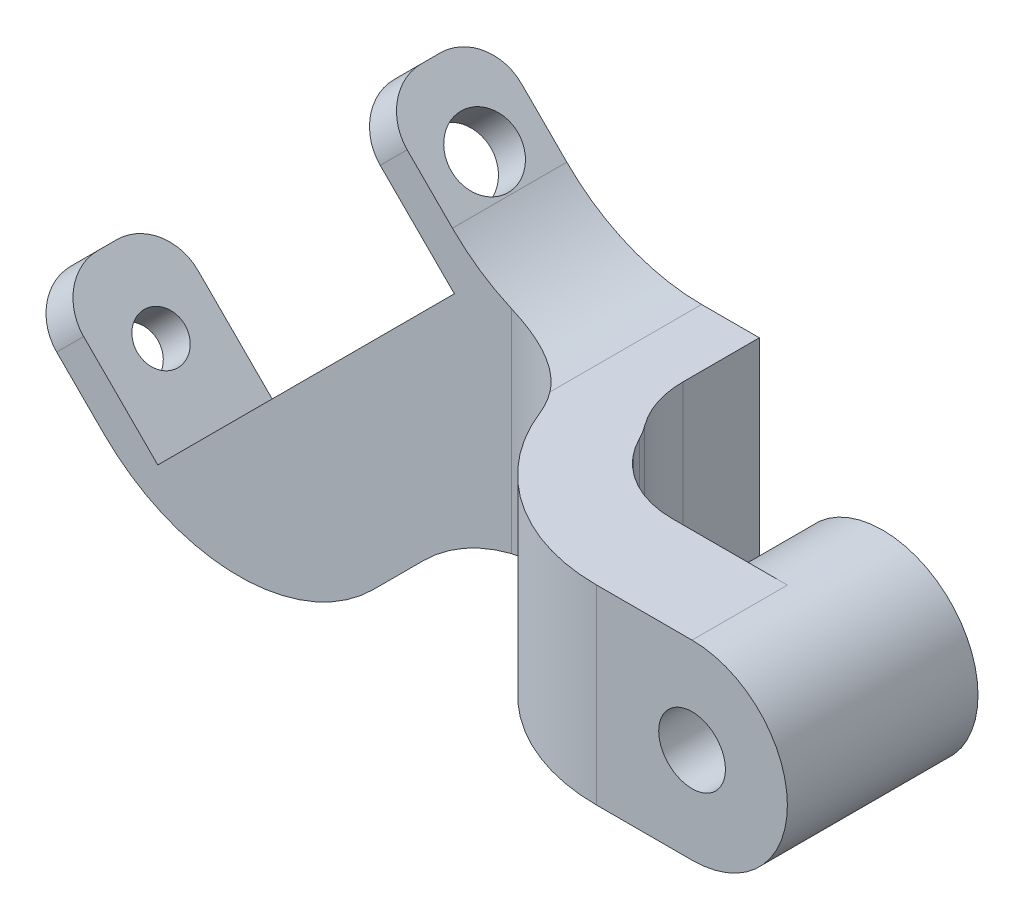
SolidWorks part; units mm, degrees
material "PET"
ref_plane "Piano frontale" through (0, 0, 0) normal (0, 0, 1) x (1, 0, 0)
ref_plane "Piano superiore" through (0, 0, 0) normal (0, 1, 0) x (1, 0, 0)
ref_plane "Piano destro" through (0, 0, 0) normal (1, 0, 0) x (0, 0, -1)
sketch "Schizzo1" plane through (0, 0, 0) normal (0, 0, 1) x (1, 0, 0)
  line L0 (0, 0) -> (-20, 0)
  line L1 (-20, 0) -> (-10, 10)
  line L2 (-10, 10) -> (10, 10)
  line L4 (10, 0) -> (0, 0)
  arc A0 (10, 0) -> (10, 10) centre (10, 5) ccw
  dimension "D6" = 10
  dimension "D1" = 20
  dimension "D2" = 10
  dimension "D3" = 10
  dimension "D4" = 0
  dimension "D5" = 20
extrude "Estrusione-Estrusione1" add sketch "Schizzo1" along normal blind 6 contours L2 A0 L4 L0 L1
sketch "Schizzo3" plane through (0, 0, 6) normal (0, 0, 1) x (1, 0, 0)
  arc A0 (10, 0) -> (10, 10) centre (10, 5) ccw construction
  arc A1 (10, 0) -> (10, 10) centre (10, 5) ccw construction
  circle A2 centre (10, 5) radius 5
  circle A3 centre (10, 5) radius 2.65
  dimension "D1" = 5.3
extrude "Estrusione-Estrusione3" add sketch "Schizzo3" against normal blind 11
sketch "Schizzo4" plane through (0, 0, 6) normal (0, 0, 1) x (1, 0, 0)
  line L0 (-10, 10) -> (-16.0795, 16.0795)
  line L1 (-20, 0) -> (-10, 10) construction
ref_plane "Piano1" through (0, 0, 0) normal (0.7071, 0.7071, 0) x (-0.7071, 0.7071, 0)
sketch "Schizzo5" plane through (0, 0, 0) normal (0.7071, 0.7071, 0) x (-0.7071, 0.7071, 0)
  line L0 (14.1421, 3) -> (18.1421, 3)
  line L1 (14.1421, 6) -> (14.1421, 0) construction
  circle A0 centre (18.1421, 3) radius 0.925
  dimension "D2" = 1.85
  dimension "D1" = 4
extrude "Estrusione-Estrusione4" add sketch "Schizzo5" against normal blind 20 separate body contours A0 region at (-12.8284, 12.8284, 2.1012)
sketch "Schizzo12" plane through (0, 0, 0) normal (0.7071, 0.7071, 0) x (-0.7071, 0.7071, 0)
  line L0 (14.1421, 0) -> (0, 0) construction
  line L1 (14.1421, 6) -> (22.1421, 6)
  line L2 (14.1421, 6) -> (14.1421, 0)
  line L3 (14.1421, 0) -> (22.1421, 0)
  line L4 (22.1421, 6) -> (22.1421, 0)
  dimension "D1" = 8
extrude "Estrusione-Estrusione6" add sketch "Schizzo12" along normal blind 2
sketch "Schizzo13" plane through (-10, 10, 0) normal (0.7071, -0.7071, 0) x (0, 0, -1)
  line L4 (-6, 0) -> (0, 0)
  line L5 (0, 0) -> (0, 2)
  line L6 (0, 2) -> (-6, 2)
  line L7 (-6, 2) -> (-6, 0)
  line L8 (-6, 0) -> (0, 0)
  line L9 (0, 0) -> (0, 2)
  line L10 (0, 2) -> (-6, 2)
  line L11 (-6, 2) -> (-6, 0)
  dimension "D1" = 0
extrude "Estrusione-Estrusione7" add sketch "Schizzo13" along normal blind 3
fillet "Raccordo2" radius 2.5 2 edges at (-14.9497, 16.364, 0) (-14.9497, 16.364, 6)
sketch "Schizzo14" plane through (1.4142, 1.4142, 0) normal (0.7071, 0.7071, 0) x (0, 0, -1)
  circle A0 centre (-3, 18.1421) radius 1.75
  circle A1 centre (-3, 18.1421) radius 0.925
  circle A2 centre (-3, 18.1421) radius 0.925
  dimension "D2" = 3.5
  dimension "D1" = 0
extrude "Taglio-Estrusione7" cut sketch "Schizzo14" against normal blind 25 contours A2 | A0 A2 | A2 | A0 region at (-11.4142, 14.2426, 4.7005) region at (-11.4142, 14.2426, 3)
sketch "Schizzo15" plane through (0, 0, 0) normal (-0.7071, -0.7071, 0) x (0, 0, 1)
  line L0 (0, 14.1421) -> (0, 19.6421) construction
  line L1 (6, 14.1421) -> (0, 14.1421)
  line L2 (6, 14.1421) -> (6, 6.1421)
  line L3 (6, 6.1421) -> (0, 6.1421)
  line L4 (0, 14.1421) -> (0, 6.1421)
  dimension "D1" = 8
extrude "Estrusione-Estrusione8" add sketch "Schizzo15" along normal blind 24
sketch "Schizzo16" plane through (-10, 10, 0) normal (-0.7071, 0.7071, 0) x (0, 0, 1)
  line L0 (0, -24) -> (0, 0) construction
  line L1 (6, -24) -> (0, -24)
  line L2 (6, -24) -> (6, -22)
  line L3 (6, -22) -> (0, -22)
  line L4 (0, -24) -> (0, -22)
  dimension "D1" = 2
extrude "Estrusione-Estrusione9" add sketch "Schizzo16" along normal up to vertex (8 mm away) up to point (-15.6569, 15.6569, 2.5)
sketch "Schizzo17" plane through (-16.9706, -16.9706, 0) normal (-0.7071, -0.7071, 0) x (0, 0, 1)
  circle A0 centre (3, 18.1421) radius 1.75 construction
  circle A1 centre (3, 18.1421) radius 1.75
  circle A2 centre (3, 18.1421) radius 1.25
  dimension "D1" = 2.5
extrude "Taglio-Estrusione8" cut sketch "Schizzo17" against normal blind 25 contours A2
fillet "Raccordo3" radius 10 1 edges at (-21.3137, -12.6274, 3)
fillet "Raccordo4" radius 10 1 edges at (-8.6863, 0, 3)
fillet "Raccordo5" radius 10 1 edges at (-7.1716, 10, 3)
fillet "Raccordo6" radius 2.5 2 edges at (-31.9203, -0.6066, 0) (-31.9203, -0.6066, 6)
sketch "Schizzo18" plane through (0, 0, 6) normal (0, 0, 1) x (1, 0, 0)
  circle A0 centre (10, 5) radius 1.75
  dimension "D1" = 3.5
extrude "Taglio-Estrusione9" cut sketch "Schizzo18" against normal through all
ref_axis "Assi1" through (-14.0659, 11.591, 3) along (0.7071, 0.7071, 0)
ref_axis "Assi2" through (-13.8891, 13.8891, 6) along (0.7071, -0.7071, 0)
ref_axis "Assi3" through (-10.1005, 12.9289, 6) along (0, 0, -1)
ref_point "Punto1"
ref_point "Punto2"
ref_axis "Assi4" through (10, 5, 0) along (0, 0, -1)
ref_axis "Assi5" through (-3.0294, 10, 6) along (1, 0, 0)
ref_point "Punto3"
sketch "Schizzo19" plane through (0, 0, 0) normal (0, 0, -1) x (-1, 0, 0)
  line L0 (-10, 5) -> (19.95, 5)
  dimension "D1" = 29.95
sketch "Schizzo20" plane through (0, 0, -5) normal (0, 0, -1) x (-1, 0, 0)
  line L1 (-20, 14.6545) -> (0, 14.6545)
  line L2 (-20, 14.6545) -> (-20, -4.6545)
  line L3 (-20, -4.6545) -> (0, -4.6545)
  line L4 (0, 14.6545) -> (0, -4.6545)
  line L5 (-20, 14.6545) -> (0, -4.6545) construction
  line L6 (-20, -4.6545) -> (0, 14.6545) construction
  point P0 (-10, 5)
  dimension "D1" = 20
extrude "Taglio-Estrusione10" cut sketch "Schizzo20" against normal through all
sketch "Schizzo21" plane through (0, 0, 6) normal (0, 0, 1) x (1, 0, 0)
  line L1 (-3.0294, 10) -> (1.9706, 10)
  line L2 (-3.0294, 10) -> (-3.0294, 0)
  line L3 (-3.0294, 0) -> (1.9706, 0)
  line L4 (1.9706, 10) -> (1.9706, 0)
  dimension "D1" = 5
extrude "Estrusione-Estrusione10" add sketch "Schizzo21" along normal blind 9.5
sketch "Schizzo22" plane through (1.9706, 0, 0) normal (1, 0, 0) x (0, 0, -1)
  line L0 (-15.5, 0) -> (-6, 0) construction
  line L1 (-15.5, 10) -> (-10.5, 10)
  line L2 (-15.5, 10) -> (-15.5, 0)
  line L3 (-15.5, 0) -> (-10.5, 0)
  line L4 (-10.5, 10) -> (-10.5, 0)
  dimension "D1" = 5
extrude "Estrusione-Estrusione11" add sketch "Schizzo22" along normal blind 15
sketch "Schizzo24" plane through (0, 0, 10.5) normal (0, 0, -1) x (-1, 0, 0)
  line L0 (-16.9706, 5) -> (-11.9706, 5)
  line L1 (-16.9706, 0) -> (-16.9706, 10) construction
  circle A0 centre (-11.9706, 5) radius 5
  circle A1 centre (-11.9706, 5) radius 2.6
  dimension "D1" = 10
  dimension "D2" = 5.2
  dimension "D3" = 5
fillet "Raccordo7" radius 5 3 edges at (1.9706, 5, 6) (16.9706, 0, 13) (16.9706, 10, 13)
fillet "Raccordo8" radius 10 1 edges at (-3.0294, 5, 15.5)
fillet "Raccordo9" radius 5 1 edges at (-3.0294, 5, 6)
extrude "Estrusione-Estrusione13" add sketch "Schizzo24" along normal blind 5 contours A1 A0 region at (11.9706, 9.8586, 10.5)
sketch "Schizzo26" plane through (0, 0, 10.5) normal (0, 0, -1) x (-1, 0, 0)
  circle A0 centre (-11.9706, 5) radius 1.75
  dimension "D1" = 3.5
extrude "Taglio-Estrusione12" cut sketch "Schizzo26" against normal through all
fillet "Raccordo10" radius 5 2 edges at (0, 5, 6) (1.9706, 5, 10.5)
sketch "Schizzo27" plane through (0, 0, 0) normal (0, 0, -1) x (-1, 0, 0)
  line L0 (-10, 5) -> (-11.9706, 5)
